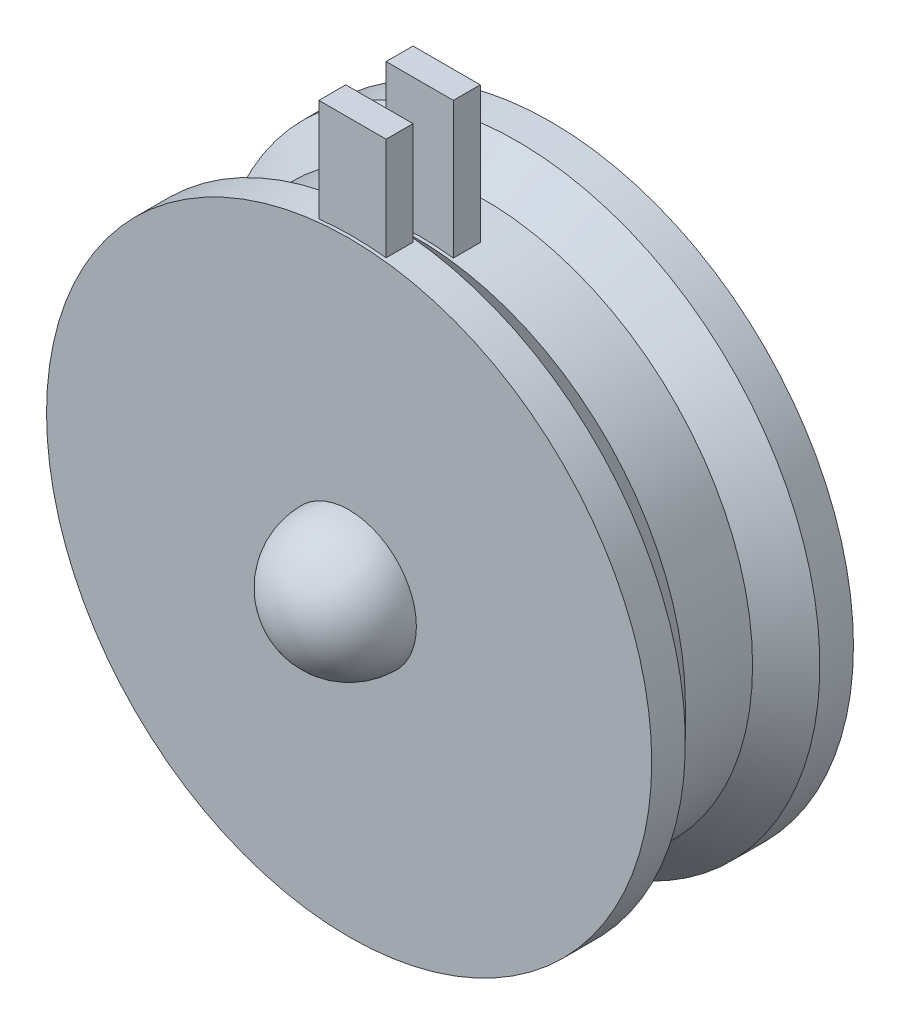
SolidWorks part; units mm, degrees
ref_plane "Front Plane" through (0, 0, 0) normal (0, 0, 1) x (1, 0, 0)
ref_plane "Top Plane" through (0, 0, 0) normal (0, 1, 0) x (1, 0, 0)
ref_plane "Right Plane" through (0, 0, 0) normal (1, 0, 0) x (0, 0, -1)
sketch "Sketch1" plane through (0, 0, 0) normal (0, 0, 1) x (1, 0, 0)
  circle A0 centre (0, 0) radius 4.5
  dimension "D1" = 9
extrude "main_base" add sketch "Sketch1" along normal blind 3
sketch "Sketch2" plane through (0, 0, 0) normal (1, 0, 0) x (0, 0, -1)
  line L0 (-2.5, 4.5) -> (-0.5, 4.5)
  line L1 (0, 4.5) -> (-3, 4.5) construction
  line L2 (-2.5, 4.5) -> (-2, 4)
  line L3 (-2, 4) -> (-1, 4)
  line L4 (-1, 4) -> (-0.5, 4.5)
  line L5 (-3, 4.5) -> (-3, -4.5) construction
  line L6 (0, -4.5) -> (0, 4.5) construction
  line L7 (0, 0) -> (-3, 0) construction
  point P13 (-1.5, 4.5)
  point P14 (-1.5, 4)
  dimension "D1" = 0.5
  dimension "D2" = 0.5
  dimension "D3" = 45
  dimension "D4" = 1
revolve "pulley_cut_out" cut sketch "Sketch2" angle 360 about L7
sketch "Sketch4" plane through (0, 0, 0) normal (0, 1, 0) x (1, 0, 0)
  line L0 (4.5, 0) -> (-4.5, 0) construction
  line L1 (-1, 0) -> (1, 0)
  line L2 (-4.5, -3) -> (4.5, -3) construction
  line L3 (-1, -3) -> (1, -3)
  line L4 (0, 1) -> (0, -4) construction
  arc A0 (1, 0) -> (-1, 0) centre (0, 0) ccw
  arc A1 (1, -3) -> (-1, -3) centre (0, -3) cw
  dimension "D1" = 2
revolve "rotating_point" add sketch "Sketch4" angle 360 about L4 region at (-0.4244, 0, -0.4244) region at (-0.4244, 0, 3.4244)
sketch "Sketch5" plane through (0, 0, 0) normal (1, 0, 0) x (0, 0, -1)
  line L2 (-2.95, 4) -> (-2.55, 4)
  line L3 (-2.95, 4) -> (-2.95, 6)
  line L4 (-2.95, 6) -> (-2.55, 6)
  line L5 (-2.55, 4) -> (-2.55, 6)
  line L6 (-3, 4.5) -> (-3, -4.5) construction
  line L7 (-2, 4) -> (-2, -4) construction
  line L8 (-1.95, 3.5) -> (-1.55, 3.5)
  line L10 (-1.95, 3.5) -> (-1.95, 6)
  line L11 (-1.95, 6) -> (-1.55, 6)
  line L12 (-1.55, 3.5) -> (-1.55, 6)
  point P12 (0, 0)
  dimension "D1" = 0.4
  dimension "D2" = 2
  dimension "D3" = 0.05
  dimension "D4" = 1.5
  dimension "D5" = 0.4
  dimension "D6" = 0.05
  dimension "D7" = 2.5
extrude "Boss-Extrude1" add sketch "Sketch5" along normal blind 0.5 and the other way blind 0.5
